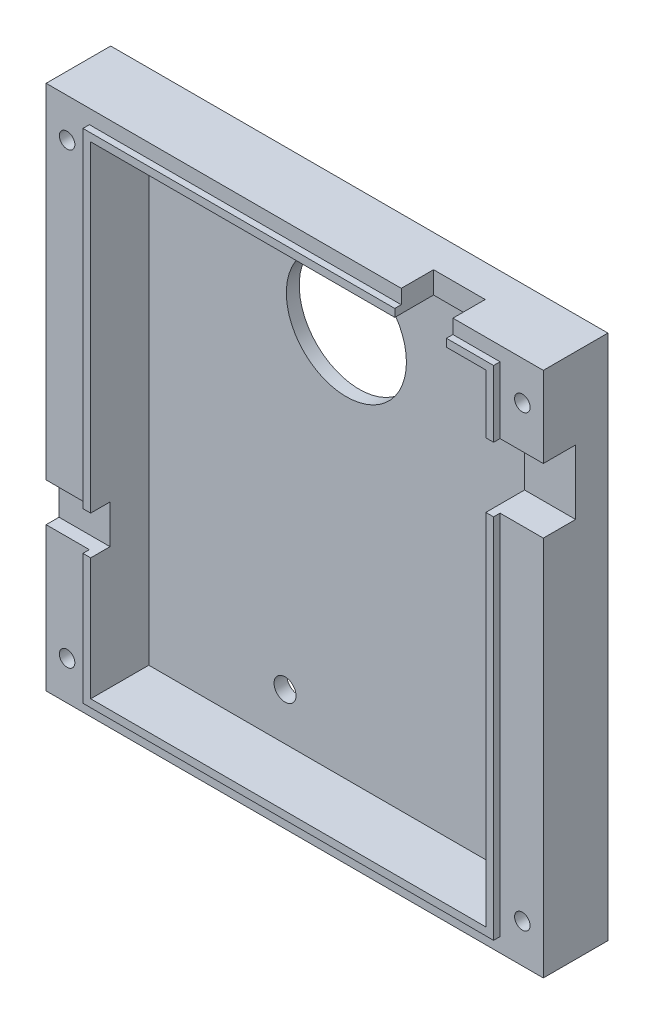
SolidWorks part; units mm, degrees
ref_plane "Front Plane" through (0, 0, 0) normal (1, 0, 0) x (0, 1, 0)
ref_plane "Top Plane" through (0, 0, 0) normal (0, 0, 1) x (0, 1, 0)
ref_plane "Right Plane" through (0, 0, 0) normal (0, 1, 0) x (-1, 0, 0)
sketch "Sketch1" plane through (0, 0, 0) normal (0, 0, 1) x (0, 1, 0)
  line L1 (0, 0) -> (81.5, 0)
  line L2 (0, 0) -> (0, -77)
  line L3 (0, -77) -> (81.5, -77)
  line L4 (81.5, 0) -> (81.5, -77)
extrude "Boss-Extrude1" add sketch "Sketch1" along normal blind 2
sketch "Sketch2" plane through (0, 0, 0) normal (0, 0, 1) x (0, 1, 0)
  line L0 (81.5, -77) -> (81.5, 0) construction
  line L1 (0, 0) -> (81.5, 0)
  line L2 (0, 0) -> (0, -6.7)
  line L3 (0, -6.7) -> (81.5, -6.7)
  line L4 (81.5, 0) -> (81.5, -6.7)
extrude "Boss-Extrude2" add sketch "Sketch2" along normal blind 8
sketch "Sketch3" plane through (0, 0, 0) normal (0, 0, 1) x (0, 1, 0)
  line L0 (0, -6.7) -> (81.5, -6.7) construction
  line L1 (0, 0) -> (22.3, 0)
  line L2 (0, 0) -> (0, -6.7)
  line L3 (0, -6.7) -> (22.3, -6.7)
  line L4 (22.3, 0) -> (22.3, -6.7)
extrude "Boss-Extrude3" add sketch "Sketch3" along normal blind 10
sketch "Sketch4" plane through (0, 0, 0) normal (0, 0, 1) x (0, 1, 0)
  line L0 (81.5, 0) -> (22.3, 0) construction
  line L1 (28.3, 0) -> (81.5, 0)
  line L2 (28.3, 0) -> (28.3, -6.7)
  line L3 (28.3, -6.7) -> (81.5, -6.7)
  line L4 (81.5, 0) -> (81.5, -6.7)
extrude "Boss-Extrude4" add sketch "Sketch4" along normal blind 10
sketch "Sketch5" plane through (0, 0, 0) normal (0, 0, 1) x (0, 1, 0)
  line L0 (0, -6.7) -> (22.3, -6.7) construction
  line L1 (2.2, -6.7) -> (79.3, -6.7)
  line L2 (2.2, -6.7) -> (2.2, -7.9)
  line L3 (2.2, -7.9) -> (79.3, -7.9)
  line L4 (79.3, -6.7) -> (79.3, -7.9)
extrude "Boss-Extrude5" add sketch "Sketch5" along normal blind 8
sketch "Sketch6" plane through (0, 0, 0) normal (0, 0, 1) x (0, 1, 0)
  line L0 (0, -6.7) -> (22.3, -6.7) construction
  line L1 (2.2, -6.7) -> (22.3, -6.7)
  line L2 (2.2, -6.7) -> (2.2, -7.9)
  line L3 (2.2, -7.9) -> (22.3, -7.9)
  line L4 (22.3, -6.7) -> (22.3, -7.9)
  line L5 (2.2, -7.9) -> (79.3, -7.9) construction
extrude "Boss-Extrude6" add sketch "Sketch6" along normal blind 11
sketch "Sketch7" plane through (0, 0, 0) normal (0, 0, 1) x (0, 1, 0)
  line L1 (28.3, -6.7) -> (79.3, -6.7)
  line L2 (28.3, -6.7) -> (28.3, -7.9)
  line L3 (28.3, -7.9) -> (79.3, -7.9)
  line L4 (79.3, -6.7) -> (79.3, -7.9)
extrude "Boss-Extrude7" add sketch "Sketch7" along normal blind 11
sketch "Sketch8" plane through (0, 0, 0) normal (0, 0, 1) x (0, 1, 0)
  line L0 (0, -6.7) -> (0, -77) construction
  line L1 (0, -70.3) -> (81.5, -70.3)
  line L2 (0, -70.3) -> (0, -77)
  line L3 (0, -77) -> (81.5, -77)
  line L4 (81.5, -70.3) -> (81.5, -77)
extrude "Boss-Extrude8" add sketch "Sketch8" along normal blind 5
sketch "Sketch9" plane through (0, 0, 0) normal (0, 0, 1) x (0, 1, 0)
  line L0 (0, -77) -> (81.5, -77) construction
  line L1 (0, -70.3) -> (59, -70.3)
  line L2 (0, -70.3) -> (0, -77)
  line L3 (0, -77) -> (59, -77)
  line L4 (59, -70.3) -> (59, -77)
extrude "Boss-Extrude9" add sketch "Sketch9" along normal blind 10
sketch "Sketch10" plane through (0, 0, 0) normal (0, 0, 1) x (0, 1, 0)
  line L0 (0, -70.3) -> (81.5, -70.3) construction
  line L1 (69, -70.3) -> (81.5, -70.3)
  line L2 (69, -70.3) -> (69, -77)
  line L3 (69, -77) -> (81.5, -77)
  line L4 (81.5, -70.3) -> (81.5, -77)
extrude "Boss-Extrude10" add sketch "Sketch10" along normal blind 10
sketch "Sketch11" plane through (0, 0, 0) normal (0, 0, 1) x (0, 1, 0)
  line L0 (0, -70.3) -> (81.5, -70.3) construction
  line L1 (2.2, -69.1) -> (79.3, -69.1)
  line L2 (2.2, -69.1) -> (2.2, -70.3)
  line L3 (2.2, -70.3) -> (79.3, -70.3)
  line L4 (79.3, -69.1) -> (79.3, -70.3)
extrude "Boss-Extrude11" add sketch "Sketch11" along normal blind 5
sketch "Sketch12" plane through (0, 0, 0) normal (0, 0, 1) x (0, 1, 0)
  line L1 (2.2, -69.1) -> (59, -69.1)
  line L2 (2.2, -69.1) -> (2.2, -70.3)
  line L3 (2.2, -70.3) -> (59, -70.3)
  line L4 (59, -69.1) -> (59, -70.3)
extrude "Boss-Extrude12" add sketch "Sketch12" along normal blind 11
sketch "Sketch13" plane through (0, 0, 0) normal (0, 0, 1) x (0, 1, 0)
  line L0 (2.2, -69.1) -> (79.3, -69.1) construction
  line L1 (69, -69.1) -> (79.3, -69.1)
  line L2 (69, -69.1) -> (69, -70.3)
  line L3 (69, -70.3) -> (79.3, -70.3)
  line L4 (79.3, -69.1) -> (79.3, -70.3)
extrude "Boss-Extrude13" add sketch "Sketch13" along normal blind 11
sketch "Sketch14" plane through (0, 0, 0) normal (0, 0, 1) x (0, 1, 0)
  line L1 (0, -6.7) -> (2.2, -6.7)
  line L2 (0, -6.7) -> (0, -70.3)
  line L3 (0, -70.3) -> (2.2, -70.3)
  line L4 (2.2, -6.7) -> (2.2, -70.3)
extrude "Boss-Extrude14" add sketch "Sketch14" along normal blind 10
sketch "Sketch15" plane through (0, 0, 0) normal (0, 0, 1) x (0, 1, 0)
  line L0 (2.2, -70.3) -> (59, -70.3) construction
  line L1 (2.2, -6.7) -> (3.4, -6.7)
  line L2 (2.2, -6.7) -> (2.2, -70.3)
  line L3 (2.2, -70.3) -> (3.4, -70.3)
  line L4 (3.4, -6.7) -> (3.4, -70.3)
extrude "Boss-Extrude15" add sketch "Sketch15" along normal blind 11
sketch "Sketch16" plane through (0, 0, 0) normal (0, 0, 1) x (0, 1, 0)
  line L1 (79.3, -6.7) -> (81.5, -6.7)
  line L2 (79.3, -6.7) -> (79.3, -70.3)
  line L3 (79.3, -70.3) -> (81.5, -70.3)
  line L4 (81.5, -6.7) -> (81.5, -70.3)
extrude "Boss-Extrude16" add sketch "Sketch16" along normal blind 5
sketch "Sketch17" plane through (0, 0, 0) normal (0, 0, 1) x (0, 1, 0)
  line L0 (81.5, -70.3) -> (81.5, -6.7) construction
  line L1 (79.3, -6.7) -> (81.5, -6.7)
  line L2 (79.3, -6.7) -> (79.3, -55)
  line L3 (79.3, -55) -> (81.5, -55)
  line L4 (81.5, -6.7) -> (81.5, -55)
extrude "Boss-Extrude17" add sketch "Sketch17" along normal blind 10
sketch "Sketch18" plane through (0, 0, 0) normal (0, 0, 1) x (0, 1, 0)
  line L0 (79.3, -69.1) -> (79.3, -7.9) construction
  line L1 (79.3, -63) -> (81.5, -63)
  line L2 (79.3, -63) -> (79.3, -70.3)
  line L3 (79.3, -70.3) -> (81.5, -70.3)
  line L4 (81.5, -63) -> (81.5, -70.3)
extrude "Boss-Extrude18" add sketch "Sketch18" along normal blind 10
sketch "Sketch19" plane through (0, 0, 0) normal (0, 0, 1) x (0, 1, 0)
  line L0 (28.3, -6.7) -> (79.3, -6.7) construction
  line L1 (78.1, -6.7) -> (79.3, -6.7)
  line L2 (78.1, -6.7) -> (78.1, -70.3)
  line L3 (78.1, -70.3) -> (79.3, -70.3)
  line L4 (79.3, -6.7) -> (79.3, -70.3)
extrude "Boss-Extrude19" add sketch "Sketch19" along normal blind 5
sketch "Sketch20" plane through (0, 0, 0) normal (0, 0, 1) x (0, 1, 0)
  line L0 (28.3, -6.7) -> (79.3, -6.7) construction
  line L1 (78.1, -6.7) -> (79.3, -6.7)
  line L2 (78.1, -6.7) -> (78.1, -55)
  line L3 (78.1, -55) -> (79.3, -55)
  line L4 (79.3, -6.7) -> (79.3, -55)
extrude "Boss-Extrude20" add sketch "Sketch20" along normal blind 11
sketch "Sketch21" plane through (0, 0, 0) normal (0, 0, 1) x (0, 1, 0)
  line L0 (78.1, -69.1) -> (78.1, -7.9) construction
  line L1 (78.1, -63) -> (79.3, -63)
  line L2 (78.1, -63) -> (78.1, -70.3)
  line L3 (78.1, -70.3) -> (79.3, -70.3)
  line L4 (79.3, -63) -> (79.3, -70.3)
extrude "Boss-Extrude21" add sketch "Sketch21" along normal blind 11
sketch "Sketch22" plane through (0, 0, 0) normal (0, 0, 1) x (0, 1, 0)
  circle A0 centre (10.7, -29) radius 1.7
extrude "Cut-Extrude1" cut sketch "Sketch22" along normal blind 17
sketch "Sketch23" plane through (0, 0, 0) normal (0, 0, 1) x (0, 1, 0)
  circle A0 centre (64, -38.5) radius 9.3
extrude "Cut-Extrude2" cut sketch "Sketch23" along normal blind 17
sketch "Sketch24" plane through (0, 0, 0) normal (0, 0, 1) x (0, 1, 0)
  circle A0 centre (6, -3.25) radius 1.2
extrude "Cut-Extrude3" cut sketch "Sketch24" along normal blind 17
sketch "Sketch25" plane through (0, 0, 0) normal (0, 0, 1) x (0, 1, 0)
  circle A0 centre (6, -3.25) radius 2
extrude "Cut-Extrude4" cut sketch "Sketch25" along normal blind 1
sketch "Sketch26" plane through (0, 0, 0) normal (0, 0, 1) x (0, 1, 0)
  circle A0 centre (75.5, -3.25) radius 1.2
extrude "Cut-Extrude5" cut sketch "Sketch26" along normal blind 17
sketch "Sketch27" plane through (0, 0, 0) normal (0, 0, 1) x (0, 1, 0)
  circle A0 centre (75.5, -3.25) radius 2
extrude "Cut-Extrude6" cut sketch "Sketch27" along normal blind 1
sketch "Sketch28" plane through (0, 0, 0) normal (0, 0, 1) x (0, 1, 0)
  circle A0 centre (6, -73.75) radius 1.2
extrude "Cut-Extrude7" cut sketch "Sketch28" along normal blind 17
sketch "Sketch29" plane through (0, 0, 0) normal (0, 0, 1) x (0, 1, 0)
  circle A0 centre (6, -73.75) radius 2
extrude "Cut-Extrude8" cut sketch "Sketch29" along normal blind 1
sketch "Sketch30" plane through (0, 0, 0) normal (0, 0, 1) x (0, 1, 0)
  circle A0 centre (75.5, -73.75) radius 1.2
extrude "Cut-Extrude9" cut sketch "Sketch30" along normal blind 17
sketch "Sketch31" plane through (0, 0, 0) normal (0, 0, 1) x (0, 1, 0)
  circle A0 centre (75.5, -73.75) radius 2
extrude "Cut-Extrude10" cut sketch "Sketch31" along normal blind 1
